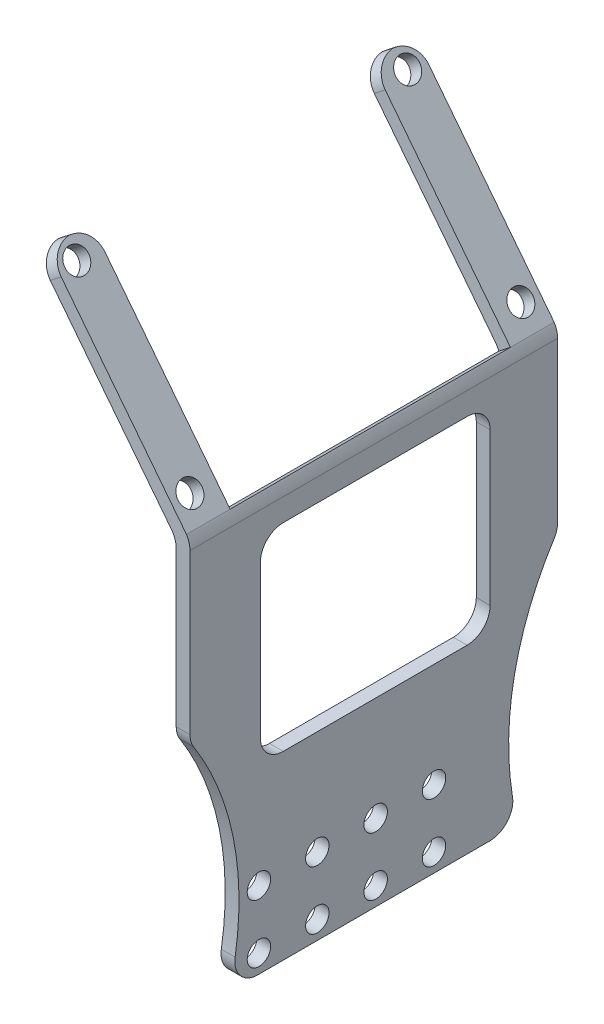
SolidWorks part; units mm, degrees
ref_plane "前视基准面" through (0, 0, 0) normal (0, 0, 1) x (1, 0, 0)
ref_plane "上视基准面" through (0, 0, 0) normal (0, 1, 0) x (1, 0, 0)
ref_plane "右视基准面" through (0, 0, 0) normal (1, 0, 0) x (0, 0, -1)
sketch "草图1" plane through (0, 0, 0) normal (0, 0, 1) x (1, 0, 0)
  line L0 (-1.182, 42.5765) -> (-31.9651, 81.977)
  line L9 (-1.5, 45) -> (1.5, 45)
  line L10 (-1.5, 45) -> (-1.5, -45)
  line L11 (-1.5, -45) -> (1.5, -45)
  line L12 (1.5, 45) -> (1.5, -45)
  line L13 (-1.5, 45) -> (1.5, -45) construction
  line L14 (-1.5, -45) -> (1.5, 45) construction
  line L15 (-31.9651, 81.977) -> (-29.6011, 83.824)
  line L16 (-29.6011, 83.824) -> (1.182, 44.4235)
  line L17 (1.182, 44.4235) -> (-1.182, 42.5765)
  line L18 (-30.7831, 82.9005) -> (0, 43.5) construction
  line L19 (0, 43.5) -> (0, -45) construction
  circle A4 centre (0, 43.5) radius 1.5 construction
  point P0 (0, 0)
  dimension "D1" = 3
  dimension "D3" = 50
  dimension "D2" = 90
  dimension "D4" = 142
extrude "凸台-拉伸1" add sketch "草图1" along normal blind 80 contours L16 L15 L0 L10 L9 | L16 L17 L0 L10 L11 L12 L9
sketch "草图2" plane through (22.2859, 17.4117, 0) normal (0.788, 0.6157, 0) x (0.6157, -0.788, 0)
  line L0 (-84.2785, -80) -> (-84.2785, 0) construction
  line L1 (-84.2785, 0) -> (-35.0101, 0) construction
  circle A0 centre (-80.2785, -4) radius 2.6
  circle A1 centre (-80.2785, -76) radius 2.6
  circle A2 centre (-40.2785, -4) radius 2.6
  circle A3 centre (-40.2785, -76) radius 2.6
  dimension "D1" = 5.2
  dimension "D2" = 72
  dimension "D3" = 4
  dimension "D4" = 4
  dimension "D5" = 40
extrude "切除-拉伸1" cut sketch "草图2" against normal through all
sketch "草图3" plane through (22.2859, 17.4117, 0) normal (0.788, 0.6157, 0) x (0.6157, -0.788, 0)
  line L0 (-84.2785, -80) -> (-84.2785, 0) construction
  line L1 (-84.2785, -9.5) -> (-35.0101, -9.5)
  line L2 (-84.2785, -9.5) -> (-84.2785, -70.5)
  line L3 (-84.2785, -70.5) -> (-35.0101, -70.5)
  line L4 (-35.0101, -9.5) -> (-35.0101, -70.5)
  line L5 (-84.2785, 0) -> (-35.0101, 0) construction
  line L6 (-84.2785, -80) -> (-35.0101, -80) construction
  line L7 (-35.0101, -80) -> (-35.0101, 0) construction
  dimension "D1" = 9.5
  dimension "D2" = 9.5
extrude "切除-拉伸2" cut sketch "草图3" against normal through all
sketch "草图4" plane through (1.5, 0, 0) normal (1, 0, 0) x (0, 0, -1)
  line L1 (-80, 45) -> (-80, -45) construction
  line L3 (-80, -45) -> (0, -45) construction
  circle A0 centre (-77.7, -28.3) radius 2.55
  circle A1 centre (-77.7, -41) radius 2.55
  circle A2 centre (-65, -28.3) radius 2.55
  circle A3 centre (-65, -41) radius 2.55
  circle A4 centre (-52.3, -28.3) radius 2.55
  circle A5 centre (-52.3, -41) radius 2.55
  circle A6 centre (-39.6, -28.3) radius 2.55
  circle A7 centre (-39.6, -41) radius 2.55
  circle A8 centre (-26.9, -28.3) radius 2.55
  circle A9 centre (-26.9, -41) radius 2.55
  circle A10 centre (-14.2, -28.3) radius 2.55
  circle A11 centre (-14.2, -41) radius 2.55
  dimension "D1" = 5.1
  dimension "D6" = 12.7
  dimension "D4" = 16.7
  dimension "D2" = 15
  dimension "D3" = 12.7
  dimension "D5" = 6
extrude "切除-拉伸3" cut sketch "草图4" against normal through all contours A2 | A4 | A6 | A8 | A9 | A7 | A5 | A3
sketch "草图5" plane through (1.5, 0, 0) normal (1, 0, 0) x (0, 0, -1)
  line L0 (-80, 45) -> (-80, -45) construction
  line L1 (-80, -45) -> (0, -45) construction
  line L2 (-80, 6.1419) -> (-80, -45)
  line L3 (-80, -45) -> (-71.4242, -45)
  line L4 (-40, 45) -> (-40, -45) construction
  line L5 (-80, 45) -> (0, 45) construction
  line L6 (0, -45) -> (-8.5758, -45)
  line L7 (0, 6.1419) -> (0, -45)
  arc A0 (-80, 6.1419) -> (-71.4242, -45) centre (-132.3387, -28.9246) cw
  arc A1 (0, 6.1419) -> (-8.5758, -45) centre (52.3387, -28.9246) ccw
  dimension "D1" = 63
extrude "切除-拉伸4" cut sketch "草图5" against normal through all
sketch "草图6" plane through (1.5, 0, 0) normal (1, 0, 0) x (0, 0, -1)
  line L0 (-80, 45) -> (0, 45) construction
  line L1 (-64.6985, 37.45) -> (-14.6985, 37.45)
  line L2 (-64.6985, 37.45) -> (-64.6985, -5.65)
  line L3 (-64.6985, -5.65) -> (-14.6985, -5.65)
  line L4 (-14.6985, 37.45) -> (-14.6985, -5.65)
  line L5 (-64.6985, 37.45) -> (-14.6985, -5.65) construction
  line L6 (-64.6985, -5.65) -> (-14.6985, 37.45) construction
  point P0 (-39.6985, 15.9)
  dimension "D1" = 29.1
  dimension "D2" = 43.1
  dimension "D3" = 50
fillet "圆角2" radius 5 2 edges at (1.5, 45, 40) (-1.5, 42.9835, 40)
extrude "切除-拉伸6" cut sketch "草图6" against normal through all
fillet "圆角3" radius 5 12 edges at (0, -5.65, 14.6985) (0, -5.65, 64.6985) (0, 37.45, 64.6985) (0, 37.45, 14.6985) (-30.7831, 82.9005, 0) (-30.7831, 82.9005, 80) (-30.7831, 82.9005, 70.5) (-30.7831, 82.9005, 9.5) (0, 6.1419, 0) (0, 6.1419, 80) (0, -45, 71.4242) (0, -45, 8.5758)
sketch "草图7" plane through (-6.5, 0, 0) normal (1, 0, 0) x (0, 0, -1)
  line L0 (-40.1805, 59.5064) -> (-40.1805, -110.2715)
  line L1 (108.8097, -110.2715) -> (-40.1805, -110.2715)
  ellipse E0 centre (108.8097, -60.1065) end of major axis (108.8097, -110.2715) minor radius 35.472 construction
